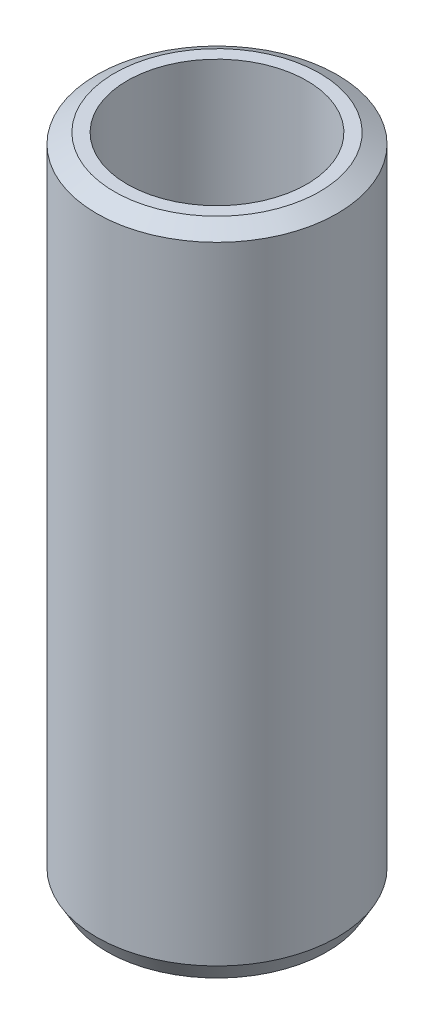
SolidWorks part; units mm, degrees
ref_plane "Front Plane" through (0, 0, 0) normal (0, 0, 1) x (1, 0, 0)
ref_plane "Top Plane" through (0, 0, 0) normal (0, 1, 0) x (1, 0, 0)
ref_plane "Right Plane" through (0, 0, 0) normal (1, 0, 0) x (0, 0, -1)
sketch "Sketch1" plane through (0, 0, 0) normal (0, 1, 0) x (1, 0, 0)
  circle A0 centre (0, 0) radius 20
  dimension "SHAFT_OD" = 40
extrude "Boss-Extrude1" add sketch "Sketch1" along normal blind 108.8575
sketch "Sketch2" plane through (0, 0, 0) normal (0, 1, 0) x (1, 0, 0)
  circle A0 centre (0, 0) radius 14.9315
  dimension "BORE_D" = 29.863
extrude "Cut-Extrude1" cut sketch "Sketch2" along normal through all
chamfer "Chamfer1" distance 1.6907 angle 60 2 edges at (0, 108.8575, 20) (0, 0, 20) first distance on face at (0, 108.8575, 20) first distance on face at (0, 0, 14.9315)
